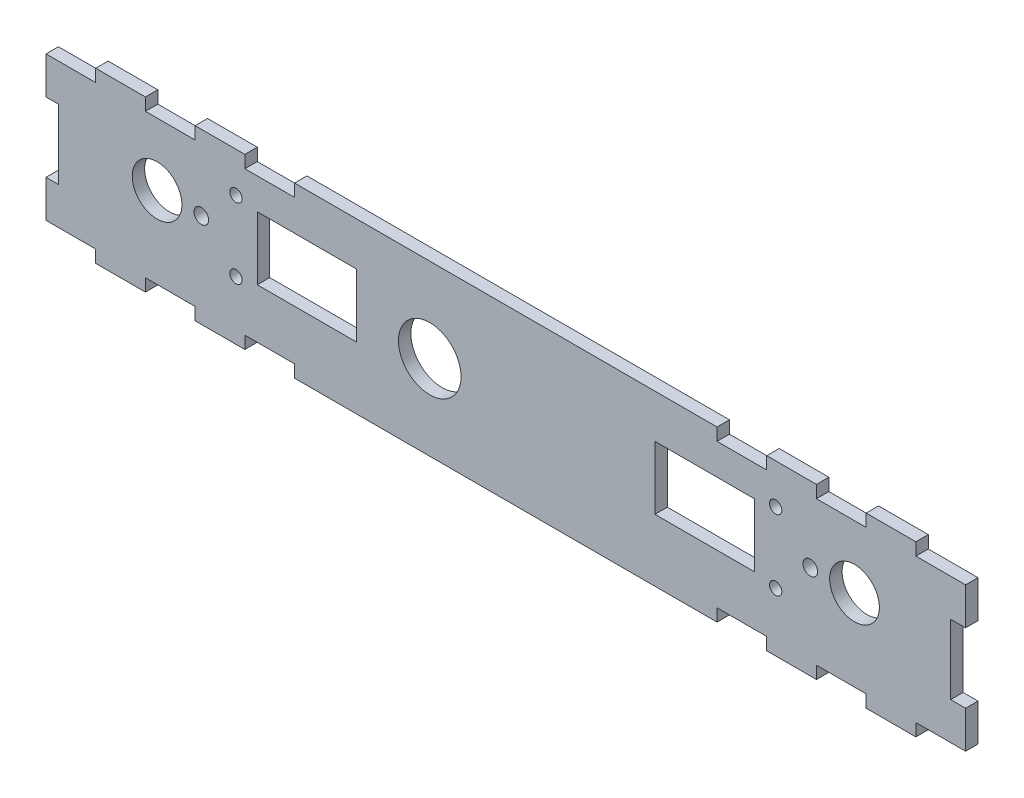
SolidWorks part; units mm, degrees
material "Acrylic (Medium-high impact)"
ref_plane "Front Plane" through (0, 0, 0) normal (0, 0, 1) x (1, 0, 0)
ref_plane "Top Plane" through (0, 0, 0) normal (0, 1, 0) x (1, 0, 0)
ref_plane "Right Plane" through (0, 0, 0) normal (1, 0, 0) x (0, 0, -1)
sketch "Sketch3" plane through (0, 0, 0) normal (0, 0, 1) x (1, 0, 0)
  line L0 (0, 22.5) -> (0, 0)
  line L1 (0, 0) -> (31.6, 0)
  line L2 (36.6, 5) -> (36.6, 17.5)
  line L3 (31.6, 22.5) -> (0, 22.5)
  line L4 (0, 0) -> (-63.5, 0) construction
  line L5 (-63.5, 0) -> (-63.5, 28.85) construction
  line L6 (-158.6, 22.5) -> (-127, 22.5)
  line L7 (0, 22.5) -> (-25.4, 22.5)
  line L8 (0, 22.5) -> (0, 0)
  line L9 (0, 0) -> (-25.4, 0)
  line L10 (-25.4, 22.5) -> (-25.4, 0)
  line L11 (-163.6, 5) -> (-163.6, 17.5)
  line L12 (-127, 0) -> (-158.6, 0)
  line L13 (-127, 22.5) -> (-127, 0)
  line L14 (-127, 0) -> (-101.6, 0)
  line L15 (-101.6, 22.5) -> (-101.6, 0)
  line L16 (-127, 22.5) -> (-101.6, 22.5)
  line L17 (-127, 22.5) -> (-127, 0)
  line L18 (-180.975, 28.85) -> (-180.975, -6.3925)
  line L21 (20.8125, -11.155) -> (58.7375, -11.155)
  line L22 (58.7375, 0) -> (58.7375, -11.155)
  line L25 (-179.3875, 28.85) -> (-185.7375, 28.85)
  line L26 (-185.7375, 22.5) -> (-185.7375, 28.85)
  line L27 (-185.7375, 28.85) -> (58.7375, 28.85)
  line L28 (-185.7375, 28.85) -> (-185.7375, -11.155)
  line L29 (-185.7375, -11.155) -> (58.7375, -11.155)
  line L30 (58.7375, 28.85) -> (58.7375, -11.155)
  line L31 (-180.975, -6.3925) -> (58.7375, -6.3925)
  line L32 (-185.7375, 24.0875) -> (53.975, 24.0875)
  line L33 (53.975, 24.0875) -> (53.975, -11.155)
  line L35 (-127, 22.5) -> (-101.6, 22.5)
  line L36 (-127, 22.5) -> (-127, 19.325)
  line L37 (-127, 19.325) -> (-101.6, 19.325)
  line L38 (-101.6, 22.5) -> (-101.6, 19.325)
  line L39 (-127, 0) -> (-101.6, 0)
  line L40 (-127, 0) -> (-127, 3.175)
  line L41 (-127, 3.175) -> (-101.6, 3.175)
  line L42 (-101.6, 0) -> (-101.6, 3.175)
  line L43 (0, 22.5) -> (-25.4, 22.5)
  line L44 (0, 22.5) -> (0, 19.325)
  line L45 (0, 19.325) -> (-25.4, 19.325)
  line L46 (-25.4, 22.5) -> (-25.4, 19.325)
  line L47 (0, 0) -> (-25.4, 0)
  line L48 (0, 0) -> (0, 3.175)
  line L49 (0, 3.175) -> (-25.4, 3.175)
  line L50 (-25.4, 0) -> (-25.4, 3.175)
  circle A2 centre (5.45, 2.25) radius 1.575
  circle A3 centre (5.45, 20.25) radius 1.575
  arc A6 (31.6, 0) -> (36.6, 5) centre (31.6, 5) ccw
  arc A7 (36.6, 17.5) -> (31.6, 22.5) centre (31.6, 17.5) ccw
  arc A8 (19.25, 11.25) -> (31.95, 11.25) centre (25.6, 11.25) ccw
  arc A9 (31.95, 11.25) -> (19.25, 11.25) centre (25.6, 11.25) ccw
  arc A10 (12.425, 11.25) -> (16.175, 11.25) centre (14.3, 11.25) ccw
  arc A11 (16.175, 11.25) -> (12.425, 11.25) centre (14.3, 11.25) ccw
  arc A12 (-143.175, 11.25) -> (-139.425, 11.25) centre (-141.3, 11.25) cw
  arc A13 (-139.425, 11.25) -> (-143.175, 11.25) centre (-141.3, 11.25) cw
  arc A14 (-158.95, 11.25) -> (-146.25, 11.25) centre (-152.6, 11.25) cw
  arc A15 (-146.25, 11.25) -> (-158.95, 11.25) centre (-152.6, 11.25) cw
  arc A16 (-163.6, 17.5) -> (-158.6, 22.5) centre (-158.6, 17.5) cw
  arc A17 (-158.6, 0) -> (-163.6, 5) centre (-158.6, 5) cw
  circle A18 centre (-132.45, 20.25) radius 1.575
  circle A19 centre (-132.45, 2.25) radius 1.575
  dimension "D3" = 5.45
  dimension "D4" = 3.15
  dimension "D8" = 3.15
  dimension "D6" = 2.25
  dimension "D9" = 1.875
  dimension "D10" = 4.7625
  dimension "D11" = 6.35
  dimension "D12" = 4.7625
  dimension "D17" = 5
  dimension "D18" = 5
  dimension "D1" = 31.6
  dimension "D2" = 36.6
  dimension "D5" = 2.25
  dimension "D7" = 5.45
  dimension "D13" = 11.25
  dimension "D14" = 14.3
  dimension "D15" = 11
  dimension "D16" = 11.25
  dimension "D19" = 22.5
  dimension "D20" = 244.475
  dimension "D21" = 30.48
  dimension "D22" = 25.4
  dimension "D23" = 3.175
  dimension "D24" = 25.4
  dimension "D25" = 3.175
  dimension "D26" = 25.4
extrude "Boss-Extrude1" add sketch "Sketch3" along normal blind 3.175 contours L33 L32 L18 L31 A7 L2 A6 L1 L9 L10 L7 L3 L12 A17 L11 A16 L6 L16 L15 L14 | A17 L12 L13 L6 A16 L11 A18 A12 A13 A14 A15 A19 | L2 A7 L3 L0 L1 A6 A11 A10 A9 A8 A2 A3 | L0 L49 L10 L9 | L45 L0 L7 L10 | L13 L37 L15 L16 | L40 L41 L42 L39 region at (16.9888, 11.25, 0) region at (-12.7, 20.9125, 0) region at (-12.7, 1.5875, 0) region at (-143.9888, 11.25, 0) region at (-114.3, 20.9125, 0) region at (-63.5, 7.3333, 0)
sketch "Sketch4" plane through (0, 0, 3.175) normal (0, 0, 1) x (1, 0, 0)
  line L0 (-155.575, 30.4375) -> (-155.575, 27.2625)
  line L1 (-180.975, 24.0875) -> (53.975, 24.0875)
  line L2 (-180.975, 24.0875) -> (-180.975, 30.4375)
  line L3 (-180.975, 30.4375) -> (53.975, 30.4375)
  line L4 (53.975, -6.3925) -> (53.975, 24.0875)
  line L5 (53.975, 24.0875) -> (-180.975, 24.0875)
  line L6 (-180.975, 24.0875) -> (-180.975, -6.3925)
  line L7 (-180.975, -6.3925) -> (53.975, -6.3925)
  line L8 (53.975, -6.3925) -> (53.975, 24.0875)
  line L9 (53.975, 24.0875) -> (-180.975, 24.0875)
  line L10 (-180.975, 24.0875) -> (-180.975, -6.3925)
  line L11 (-180.975, -6.3925) -> (53.975, -6.3925)
  line L12 (53.975, 24.0875) -> (53.975, 30.4375)
  line L13 (-180.975, 30.4375) -> (53.975, 30.4375)
  line L14 (-180.975, 30.4375) -> (-180.975, 27.2625)
  line L15 (-180.975, 27.2625) -> (53.975, 27.2625)
  line L16 (53.975, 30.4375) -> (53.975, 27.2625)
  line L17 (-180.975, 30.4375) -> (-168.275, 30.4375)
  line L18 (-180.975, 30.4375) -> (-180.975, 27.2625)
  line L19 (-180.975, 27.2625) -> (-168.275, 27.2625)
  line L20 (-168.275, 30.4375) -> (-168.275, 27.2625)
  line L21 (-155.575, 30.4375) -> (-142.875, 30.4375)
  line L22 (-142.875, 30.4375) -> (-142.875, 27.2625)
  line L23 (-155.575, 27.2625) -> (-142.875, 27.2625)
  line L24 (-130.175, 30.4375) -> (-130.175, 27.2625)
  line L25 (-130.175, 30.4375) -> (-117.475, 30.4375)
  line L26 (-117.475, 30.4375) -> (-117.475, 27.2625)
  line L27 (-130.175, 27.2625) -> (-117.475, 27.2625)
  line L28 (28.575, 27.2625) -> (28.575, 30.4375)
  line L29 (53.975, 27.2625) -> (41.275, 27.2625)
  line L30 (53.975, 27.2625) -> (53.975, 30.4375)
  line L31 (53.975, 30.4375) -> (41.275, 30.4375)
  line L32 (41.275, 27.2625) -> (41.275, 30.4375)
  line L33 (28.575, 27.2625) -> (15.875, 27.2625)
  line L34 (15.875, 27.2625) -> (15.875, 30.4375)
  line L35 (28.575, 30.4375) -> (15.875, 30.4375)
  line L36 (3.175, 27.2625) -> (3.175, 30.4375)
  line L37 (3.175, 27.2625) -> (-9.525, 27.2625)
  line L38 (-9.525, 27.2625) -> (-9.525, 30.4375)
  line L39 (3.175, 30.4375) -> (-9.525, 30.4375)
  line L40 (-180.975, 8.8475) -> (49.4654, 8.8475) construction
  line L41 (3.175, -12.7425) -> (-9.525, -12.7425)
  line L42 (-9.525, -9.5675) -> (-9.525, -12.7425)
  line L43 (3.175, -9.5675) -> (-9.525, -9.5675)
  line L44 (3.175, -9.5675) -> (3.175, -12.7425)
  line L45 (28.575, -12.7425) -> (15.875, -12.7425)
  line L46 (15.875, -9.5675) -> (15.875, -12.7425)
  line L47 (28.575, -9.5675) -> (15.875, -9.5675)
  line L48 (41.275, -9.5675) -> (41.275, -12.7425)
  line L49 (53.975, -12.7425) -> (41.275, -12.7425)
  line L50 (53.975, -9.5675) -> (53.975, -12.7425)
  line L51 (53.975, -9.5675) -> (41.275, -9.5675)
  line L52 (28.575, -9.5675) -> (28.575, -12.7425)
  line L53 (-130.175, -9.5675) -> (-117.475, -9.5675)
  line L54 (-117.475, -12.7425) -> (-117.475, -9.5675)
  line L55 (-130.175, -12.7425) -> (-117.475, -12.7425)
  line L56 (-130.175, -12.7425) -> (-130.175, -9.5675)
  line L57 (-155.575, -9.5675) -> (-142.875, -9.5675)
  line L58 (-142.875, -12.7425) -> (-142.875, -9.5675)
  line L59 (-155.575, -12.7425) -> (-142.875, -12.7425)
  line L60 (-168.275, -12.7425) -> (-168.275, -9.5675)
  line L61 (-180.975, -9.5675) -> (-168.275, -9.5675)
  line L62 (-180.975, -12.7425) -> (-180.975, -9.5675)
  line L63 (-180.975, -12.7425) -> (-168.275, -12.7425)
  line L64 (53.975, -12.7425) -> (53.975, -9.5675)
  line L65 (-180.975, -9.5675) -> (53.975, -9.5675)
  line L66 (-180.975, -12.7425) -> (-180.975, -9.5675)
  line L67 (-180.975, -12.7425) -> (53.975, -12.7425)
  line L68 (53.975, -6.3925) -> (53.975, -12.7425)
  line L69 (53.975, -6.3925) -> (-180.975, -6.3925)
  line L70 (-180.975, -12.7425) -> (53.975, -12.7425)
  line L71 (-180.975, -6.3925) -> (-180.975, -12.7425)
  line L72 (-180.975, -6.3925) -> (53.975, -6.3925)
  line L73 (-155.575, -12.7425) -> (-155.575, -9.5675)
  line M29 (53.975, 24.0875) -> (-180.975, 24.0875)
  line M31 (-180.975, -6.3925) -> (53.975, -6.3925)
  dimension "D2" = 6.35
  dimension "D3" = 3.175
  dimension "D4" = 12.7
  dimension "D5" = 3
  dimension "D6" = 12.7
  dimension "D7" = 3
  dimension "D1" = 0
extrude "Boss-Extrude2" add sketch "Sketch4" against normal blind 3.175 contours L15 L38 L13 L26 | L24 L13 L22 L15 | L13 L20 L15 L0 | L15 L2 L12 M29 | L36 L15 L34 L3 | L15 L32 L3 L28 | L71 L61 L65 L57 L53 L43 L47 L51 L68 M31 | L52 L67 L48 L65 | L44 L67 L46 L65 | L54 L67 L42 L65 | L58 L67 L56 L65 | L67 L73 L65 L60 region at (-161.925, 28.85, 3.175) region at (-63.5, 25.675, 3.175) region at (-136.525, 28.85, 3.175) region at (-63.5, 28.85, 3.175) region at (-63.5, -7.98, 3.175) region at (9.525, 28.85, 3.175) region at (34.925, 28.85, 3.175) region at (-161.925, -11.155, 3.175) region at (34.925, -11.155, 3.175) region at (-136.525, -11.155, 3.175) region at (9.525, -11.155, 3.175) region at (-63.5, -11.155, 3.175)
sketch "Sketch5" plane through (0, 0, 3.175) normal (0, 0, 1) x (1, 0, 0)
  line L0 (53.975, 27.2625) -> (53.975, -9.5675) construction
  line L1 (-168.275, -12.7425) -> (-180.975, -12.7425)
  line L2 (-168.275, -12.7425) -> (-168.275, -0.0425)
  line L3 (-168.275, -0.0425) -> (-180.975, -0.0425)
  line L4 (-180.975, -12.7425) -> (-180.975, -0.0425)
  line L5 (-180.975, 27.2625) -> (-180.975, -9.5675) construction
  line L6 (-168.275, 30.4375) -> (-180.975, 30.4375)
  line L7 (-168.275, 30.4375) -> (-168.275, 17.7375)
  line L8 (-168.275, 17.7375) -> (-180.975, 17.7375)
  line L9 (-180.975, 30.4375) -> (-180.975, 17.7375)
  line L10 (41.275, 30.4375) -> (53.975, 30.4375)
  line L11 (41.275, 30.4375) -> (41.275, 17.7375)
  line L12 (41.275, 17.7375) -> (53.975, 17.7375)
  line L13 (53.975, 30.4375) -> (53.975, 17.7375)
  line L15 (41.275, -12.7425) -> (53.975, -12.7425)
  line L16 (41.275, -12.7425) -> (41.275, -0.0425)
  line L17 (41.275, -0.0425) -> (53.975, -0.0425)
  line L18 (53.975, -12.7425) -> (53.975, -0.0425)
  line L19 (-180.975, 17.7375) -> (-177.8, 17.7375)
  line L20 (-180.975, 17.7375) -> (-180.975, -0.0425)
  line L21 (-180.975, -0.0425) -> (-177.8, -0.0425)
  line L22 (-177.8, 17.7375) -> (-177.8, -0.0425)
  line L23 (53.975, 17.7375) -> (50.165, 17.7375)
  line L24 (53.975, 17.7375) -> (53.975, -0.0425)
  line L25 (53.975, -0.0425) -> (50.165, -0.0425)
  line L26 (50.165, 17.7375) -> (50.165, -0.0425)
  dimension "D1" = 12.7
  dimension "D2" = 12.7
  dimension "D3" = 12.7
  dimension "D4" = 3.175
  dimension "D5" = 3.81
extrude "Cut-Extrude1" cut sketch "Sketch5" against normal blind 7.62 contours L22 L8 L20 L3 | L12 L26 L17 L24 region at (-179.3875, 8.8475, 3.175) region at (52.07, 8.8475, 3.175)
sketch "Sketch6" plane through (0, 0, 0) normal (0, 0, -1) x (-1, 0, 0)
  line L0 (180.975, 27.2625) -> (70.612, 27.2625)
  line L1 (180.975, -9.5675) -> (95.25, -9.5675)
  line L3 (95.25, -9.5675) -> (70.612, -9.5675)
  line L4 (95.25, -9.5675) -> (95.25, 27.2625)
  line L5 (95.25, 27.2625) -> (70.612, 27.2625)
  line L6 (70.612, -9.5675) -> (70.612, 27.2625)
  circle A0 centre (82.931, 8.8475) radius 8
  dimension "16mm" = 16
  dimension "D1" = 110.363
  dimension "D2" = 85.725
extrude "Cut-Extrude2" cut sketch "Sketch6" against normal blind 5.08 contours A0 region at (-82.931, 8.8475, 0)
